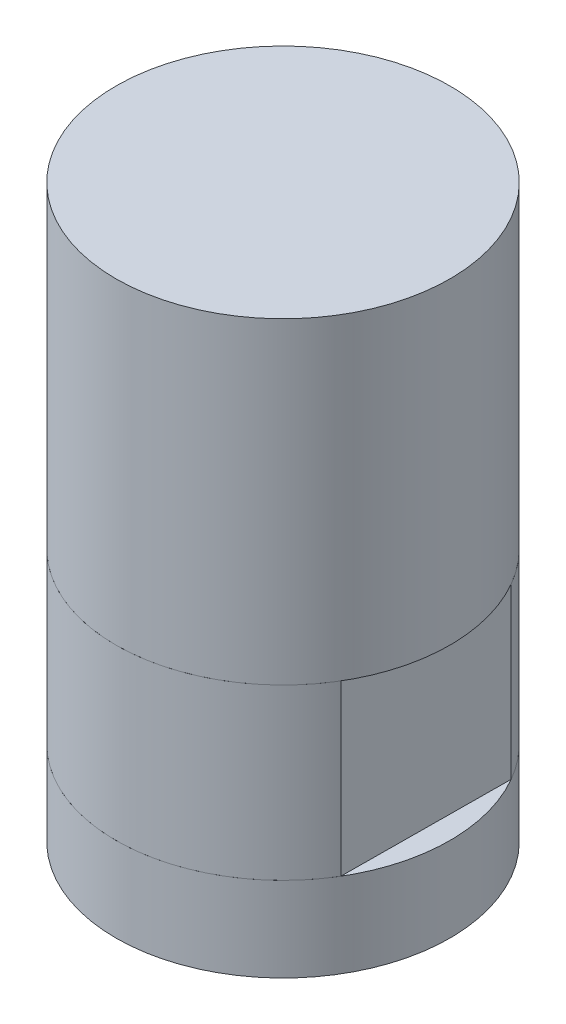
SolidWorks part; units mm, degrees
ref_plane "Front Plane" through (0, 0, 0) normal (0, 0, 1) x (1, 0, 0)
ref_plane "Top Plane" through (0, 0, 0) normal (0, 1, 0) x (1, 0, 0)
ref_plane "Right Plane" through (0, 0, 0) normal (1, 0, 0) x (0, 0, -1)
sketch "Sketch1" plane through (0, 0, 0) normal (0, 1, 0) x (1, 0, 0)
  circle A0 centre (0, 0) radius 3.95
  dimension "D1" = 7.9
extrude "Boss-Extrude1" add sketch "Sketch1" along normal blind 2 contours A0
sketch "Sketch3" plane through (0, 2, 0) normal (0, 1, 0) x (1, 0, 0)
  line L2 (-2.0256, 3.3911) -> (1.9744, 3.4212)
  line L3 (3.4212, 1.9744) -> (3.3911, -2.0256)
  arc A2 (-2.0256, 3.3911) -> (3.3911, -2.0256) centre (0, 0) ccw
  arc A3 (3.4212, 1.9744) -> (1.9744, 3.4212) centre (0, 0) ccw
  point P3 (3.4212, 1.9744)
  point P4 (3.3911, -2.0256)
  point P5 (1.9744, 3.4212)
  point P6 (-2.0256, 3.3911)
  dimension "D3" = 3.95
  dimension "D1" = 4
  dimension "D2" = 4
extrude "Boss-Extrude2" add sketch "Sketch3" along normal blind 4
sketch "Sketch4" plane through (0, 6, 0) normal (0, 1, 0) x (1, 0, 0)
  circle A0 centre (0, 0) radius 3.95
  dimension "D1" = 7.9
extrude "Boss-Extrude3" add sketch "Sketch4" along normal blind 2
sketch "Sketch5" plane through (0, 8, 0) normal (0, 1, 0) x (1, 0, 0)
  line L0 (-2.2, 0) -> (1.6762, 0) construction
  line L2 (1.6762, 1.4249) -> (1.6762, -1.4249)
  arc A1 (1.6762, 1.4249) -> (1.6762, -1.4249) centre (0, 0) ccw
  dimension "D1" = 2.2
extrude "Cut-Extrude1" cut sketch "Sketch5" against normal through all
sketch "Sketch6" plane through (0, 8, 0) normal (0, 1, 0) x (1, 0, 0)
  circle A0 centre (0, 0) radius 3.95
extrude "Boss-Extrude4" add sketch "Sketch6" along normal blind 5.5
